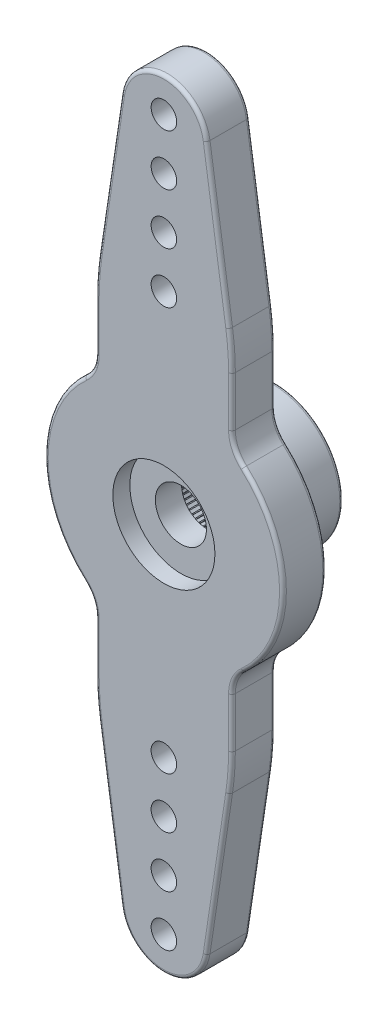
SolidWorks part; units mm, degrees
ref_plane "Ön Düzlem" through (0, 0, 0) normal (0, 0, 1) x (1, 0, 0)
ref_plane "Üst Düzlem" through (0, 0, 0) normal (0, 1, 0) x (1, 0, 0)
ref_plane "Sağ Düzlem" through (0, 0, 0) normal (1, 0, 0) x (0, 0, -1)
sketch "Sketch1" plane through (0, 0, 0) normal (0, 0, 1) x (1, 0, 0)
  line L0 (-4, 10.7446) -> (-4, 5.7446)
  line L1 (4, 10.7446) -> (4, 5.7446)
  line L2 (0, 0) -> (0, 20.32) construction
  line L3 (-4, 5.7446) -> (4, 5.7446) construction
  line L4 (-2.5121, 20.6956) -> (-4, 10.7446)
  line L5 (2.5121, 20.6956) -> (4, 10.7446)
  circle A0 centre (0, 0) radius 7
  circle A1 centre (0, 0) radius 22.86
  circle A2 centre (0, 20.32) radius 2.54
  circle A3 centre (0, 0) radius 1.5
  dimension "D1" = 45.72
  dimension "D2" = 14
  dimension "D3" = 5.08
  dimension "D5" = 3
  dimension "D4" = 5
  dimension "D6" = 8
extrude "Boss-Extrude1" add sketch "Sketch1" along normal blind 2.54 contours A0 A3 | A2 L4 L0 A0 L1 L5 | A2 region at (0, 12.1859, 0) region at (0, 6.802, 0) region at (0, 20.32, 0)
fillet "Fillet1" radius 15 2 edges at (-4, 10.7446, 1.27) (4, 10.7446, 1.27)
sketch "Sketch2" plane through (0, 0, 2.54) normal (0, 0, 1) x (1, 0, 0)
  line L0 (0, 0) -> (0, 22.86) construction
  arc A0 (2.5121, 20.6956) -> (-2.5121, 20.6956) centre (0, 20.32) ccw construction
  circle A1 centre (0, 20.86) radius 0.75
  circle A2 centre (0, 17.86) radius 0.75
  circle A3 centre (0, 14.86) radius 0.75
  circle A4 centre (0, 11.86) radius 0.75
  dimension "D1" = 1.5
  dimension "D2" = 2
  dimension "D3" = 4
extrude "Cut-Extrude1" cut sketch "Sketch2" against normal through all
pattern_circular "CirPattern2" count 2 over 360 about axis through (0, 0, 2.54) along (0, 0, 1) of "Boss-Extrude1", "Fillet1", "Cut-Extrude1"
fillet "Fillet2" radius 2 4 edges at (4, 5.7446, 1.27) (-4, 5.7446, 1.27) (-4, -5.7446, 1.27) (4, -5.7446, 1.27)
sketch "Sketch3" plane through (0, 0, 2.54) normal (0, 0, 1) x (1, 0, 0)
  circle A0 centre (0, 0) radius 3
  dimension "D1" = 6
extrude "Cut-Extrude2" cut sketch "Sketch3" against normal blind 1
sketch "Sketch4" plane through (0, 0, 0) normal (0, 0, -1) x (-1, 0, 0)
  circle A0 centre (0, 0) radius 4
  circle A1 centre (0, 0) radius 3
  dimension "D1" = 8
  dimension "D2" = 6
extrude "Boss-Extrude2" add sketch "Sketch4" along normal blind 4
sketch "Sketch5" plane through (0, 0, -4) normal (0, 0, -1) x (-1, 0, 0)
  line L0 (0, 0) -> (0, -4) construction
  line L2 (0.025, -2.8941) -> (-0.025, -2.8941)
  line L3 (0.025, -2.8941) -> (0.025, -3.3941)
  line L4 (0.025, -3.3941) -> (-0.025, -3.3941)
  line L5 (-0.025, -2.8941) -> (-0.025, -3.3941)
  line L6 (0.025, -2.8941) -> (-0.025, -3.3941) construction
  line L7 (0.025, -3.3941) -> (-0.025, -2.8941) construction
  circle A1 centre (0, 0) radius 4 construction
  point P0 (0, -3.1441)
  dimension "D1" = 0.05
  dimension "D2" = 0.5
extrude "Boss-Extrude3" add sketch "Sketch5" against normal up to surface (4 mm away) up to face at (-3, 0, 0)
pattern_circular "CirPattern3" count 80 over 360 about axis through (0, 0, -4) along (0, 0, -1) of "Boss-Extrude3"
fillet "Fillet3" radius 0.2 42 edges at (0, 22.86, 0) (-3.1736, 16.2716, 0) (-3.9587, 10.7415, 0) (-4, 8.1688, 0) (-4.1743, 5.8917, 0) (-7, 0, 0) (-4.1743, -5.8917, 0) (-4, -8.1688, 0) (-3.9587, -10.7415, 0) (-3.1736, -16.2716, 0) (0, -22.86, 0) (3.1736, -16.2716, 0) (3.9587, -10.7415, 0) (4, -8.1688, 0) (4.1743, -5.8917, 0) (7, 0, 0) (4.1743, 5.8917, 0) (4, 8.1688, 0) (3.9587, 10.7415, 0) (0, 22.86, 2.54) (-3.1736, 16.2716, 2.54) (-3.9587, 10.7415, 2.54) (-4, 8.1688, 2.54) (-4.1743, 5.8917, 2.54) (-7, 0, 2.54) (-4.1743, -5.8917, 2.54) (-4, -8.1688, 2.54) (-3.9587, -10.7415, 2.54) (-3.1736, -16.2716, 2.54) (0, -22.86, 2.54) (3.1736, -16.2716, 2.54) (3.9587, -10.7415, 2.54) (4, -8.1688, 2.54) (4.1743, -5.8917, 2.54) (7, 0, 2.54) (4.1743, 5.8917, 2.54) (4, 8.1688, 2.54) (3.9587, 10.7415, 2.54) (3.1736, 16.2716, 0) (3.1736, 16.2716, 2.54) (4, 0, 0) (-4, 0, -4)
